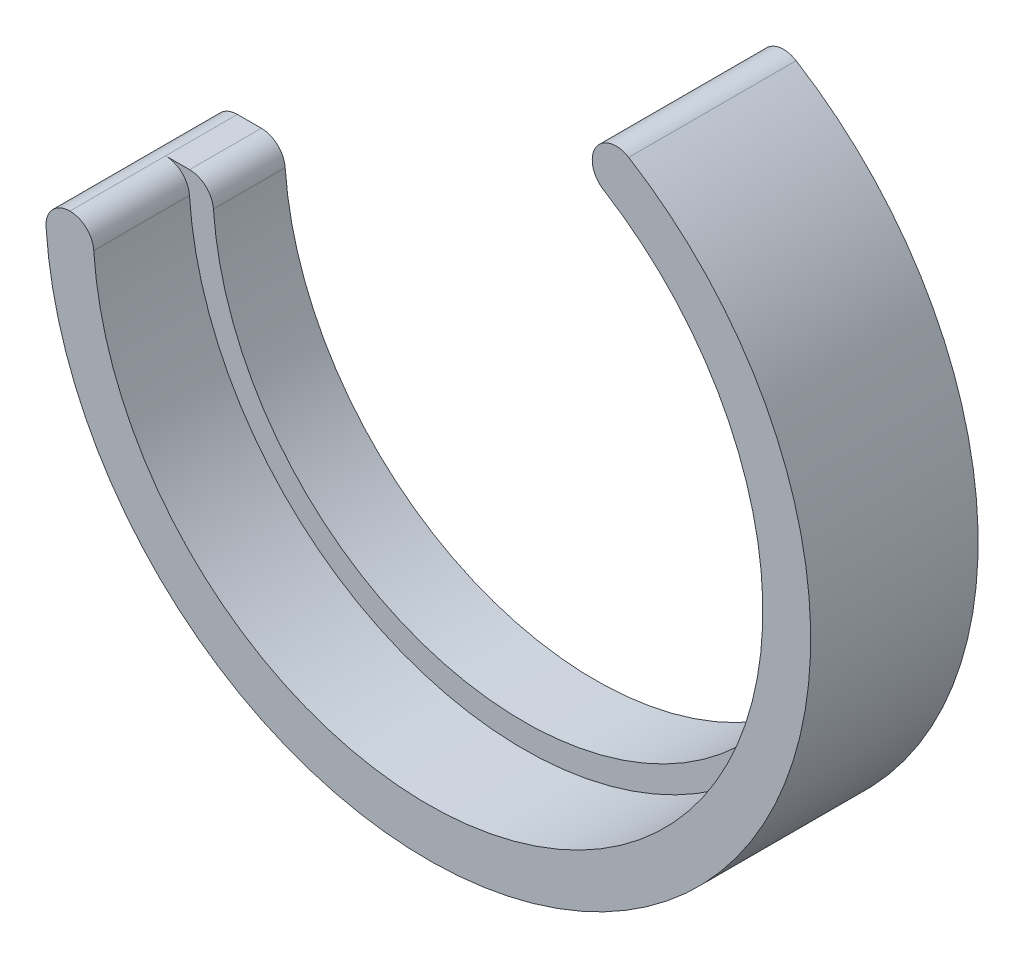
SolidWorks part; units mm, degrees
ref_plane "Front Plane" through (0, 0, 0) normal (0, 0, 1) x (1, 0, 0)
ref_plane "Top Plane" through (0, 0, 0) normal (0, 1, 0) x (1, 0, 0)
ref_plane "Right Plane" through (0, 0, 0) normal (1, 0, 0) x (0, 0, -1)
sketch "Sketch1" plane through (0, 0, 0) normal (0, 0, 1) x (1, 0, 0)
  line L0 (3.7329, 7.0757) -> (3.033, 5.749)
  line L1 (-8, 0) -> (-6.5, 0)
  arc A0 (3.033, 5.749) -> (-6.5, 0) centre (0, 0) cw
  arc A1 (3.7329, 7.0757) -> (-8, 0) centre (0, 0) cw
  dimension "D1" = 1.5
extrude "Boss-Extrude1" add sketch "Sketch1" along normal blind 1.5
ref_plane "Plane1" through (0, 0, 1.5) normal (0, 0, 1) x (1, 0, 0)
sketch "Sketch2" plane through (0, 0, 1.5) normal (0, 0, 1) x (1, 0, 0)
  line L2 (3.7329, 7.0757) -> (3.2663, 6.1912)
  line L3 (-7, 0) -> (-8, 0)
  arc A0 (3.2663, 6.1912) -> (-7, 0) centre (0, 0) cw
  arc A3 (3.7329, 7.0757) -> (-8, 0) centre (0, 0) cw
  dimension "D1" = 7
  dimension "D2" = 1
extrude "Boss-Extrude2" add sketch "Sketch2" along normal blind 2
fillet "Fillet1" radius 0.5 6 edges at (-6.5, 0, 0.75) (-8, 0, 1.75) (3.033, 5.749, 0.75) (3.7329, 7.0757, 1.75)
